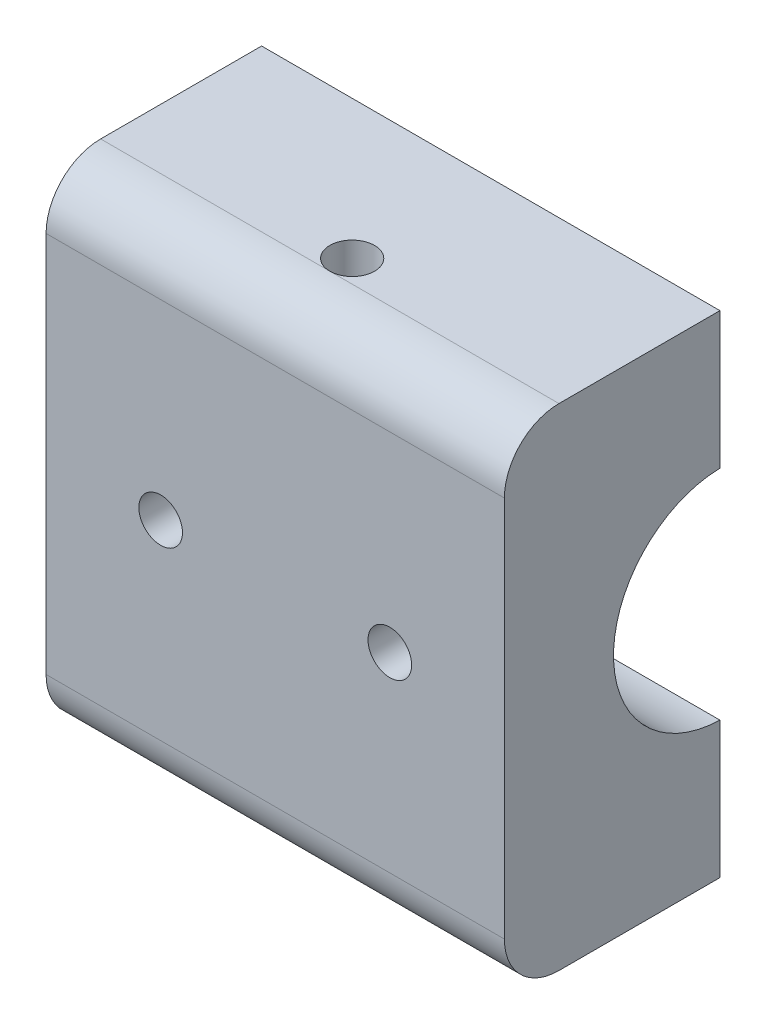
SolidWorks part; units mm, degrees
material "Onyx"
ref_plane "Front Plane" through (0, 0, 0) normal (0, 0, 1) x (1, 0, 0)
ref_plane "Top Plane" through (0, 0, 0) normal (0, 1, 0) x (1, 0, 0)
ref_plane "Right Plane" through (0, 0, 0) normal (1, 0, 0) x (0, 0, -1)
sketch "Sketch1" plane through (0, 0, 0) normal (1, 0, 0) x (0, 0, -1)
  line L0 (0, 22.5) -> (0, -22.5) construction
  line L1 (-0.25, 22.5) -> (-0.25, 9.9969)
  line L2 (-0.25, -9.9969) -> (-0.25, -22.5)
  line L4 (-0.25, 22.5) -> (-0.25, -22.5) construction
  line L6 (-20, 17.5) -> (-20, -17.5)
  line L8 (0, 22.5) -> (-15, 22.5)
  line L10 (0, 0) -> (-20, 0) construction
  line L12 (0, -22.5) -> (-15, -22.5)
  arc A1 (0, 10) -> (0, -10) centre (0, 0) ccw
  circle A3 centre (0, 0) radius 10 construction
  arc A4 (-15, 22.5) -> (-20, 17.5) centre (-15, 17.5) ccw
  arc A5 (-20, -17.5) -> (-15, -22.5) centre (-15, -17.5) ccw
  point P23 (-10, 0)
  dimension "D2" = 45
  dimension "D4" = 5
  dimension "D3" = 20
  dimension "D1" = 0.25
extrude "Boss-Extrude1" add sketch "Sketch1" against normal blind 42 contours A1 L1 L2 region at (0, 0, 11.1992)
sketch "Sketch4" plane through (0, 0, 20) normal (0, 0, 1) x (1, 0, 0)
  circle A0 centre (-10.5, 0) radius 2
  circle A1 centre (-31.5, 0) radius 2
  circle A2 centre (-10.5, 0) radius 2 construction
extrude "Cut-Extrude4" cut sketch "Sketch4" against normal through all
sketch "Sketch5" plane through (0, -22.5, 0) normal (0, -1, 0) x (1, 0, 0)
  line L0 (-21, 20) -> (-21, 0.25) construction
  line L3 (-42, 20) -> (0, 20) construction
  line L4 (-42, 0.25) -> (0, 0.25) construction
  line L5 (-42, 15) -> (0, 15) construction
  circle A0 centre (-21, 12.95) radius 2.05
  dimension "D1" = 4.1
extrude "Cut-Extrude5" cut sketch "Sketch5" against normal through all
